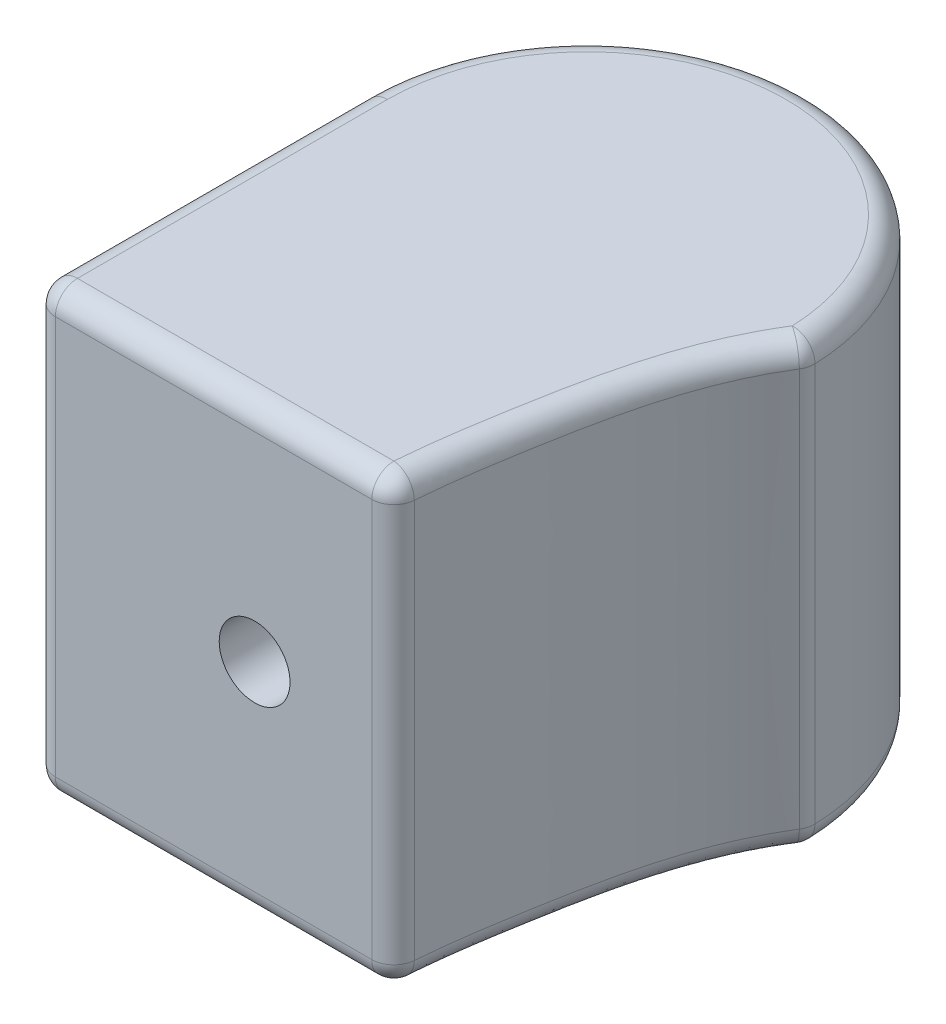
SolidWorks part; units mm, degrees
ref_plane "Front Plane" through (0, 0, 0) normal (0, 0, 1) x (1, 0, 0)
ref_plane "Top Plane" through (0, 0, 0) normal (0, 1, 0) x (1, 0, 0)
ref_plane "Right Plane" through (0, 0, 0) normal (1, 0, 0) x (0, 0, -1)
sketch "Sketch1" plane through (0, 0, 0) normal (0, 1, 0) x (1, 0, 0)
  line L0 (0, 0) -> (0, 32.8986) construction
  line L5 (10, 0) -> (-10, 0)
  line L6 (-10, 0) -> (-10, 15)
  line L7 (10, 0) -> (10, 15)
  arc A0 (-10, 15) -> (10, 15) centre (0, 15) cw
  spline S0 degree 3 poles (10, 15) (8.1791, 12.2077) (7.122, 7.0798) (6.3179, 1.9506) (6.2319, 0) knots 0 0 0 0 0.62502 1 1 1 1
  point P12 (0, 0)
  dimension "D1" = 10
  dimension "D2" = 15
extrude "Boss-Extrude1" add sketch "Sketch1" along normal mid plane 20 contours L0 L5 S0 A0 | L5 L0 A0 L6 region at (-4.7402, 0, -11.536) region at (3.9982, 0, -12.6647)
ref_point "Point1"
sketch "Sketch2" plane through (0, 0, 0) normal (0, 0, 1) x (1, 0, 0)
  circle A0 centre (0, 0) radius 1.6
  dimension "D1" = 3.2
extrude "Cut-Extrude1" cut sketch "Sketch2" against normal blind 5 and the other way through all
fillet "Fillet1" radius 1 11 edges at (0, 10, -25) (0, -10, -25) (-10, 10, -7.5) (-10, 0, 0) (-10, -10, -7.5) (6.2319, 0, 0) (10, 0, -15) (-1.8841, -10, 0) (-1.8841, 10, 0)
